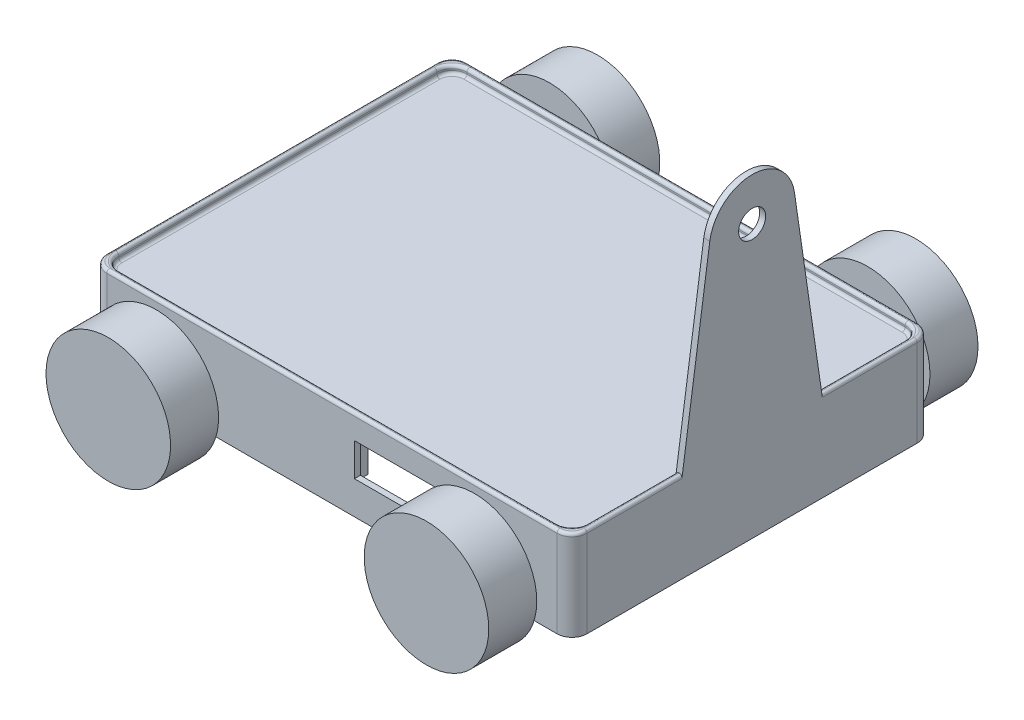
SolidWorks part; units mm, degrees
ref_plane "Front Plane" through (0, 0, 0) normal (0, 0, 1) x (1, 0, 0)
ref_plane "Top Plane" through (0, 0, 0) normal (0, 1, 0) x (1, 0, 0)
ref_plane "Right Plane" through (0, 0, 0) normal (1, 0, 0) x (0, 0, -1)
sketch "Sketch1" plane through (0, 0, 0) normal (0, 1, 0) x (1, 0, 0)
  line L1 (-160, 120) -> (160, 120)
  line L2 (-160, 120) -> (-160, -120)
  line L3 (-160, -120) -> (160, -120)
  line L4 (160, 120) -> (160, -120)
  line L5 (-160, 120) -> (160, -120) construction
  line L6 (-160, -120) -> (160, 120) construction
  point P0 (0, 0)
  dimension "D1" = 320
  dimension "D2" = 240
extrude "Boss-Extrude1" add sketch "Sketch1" along normal blind 5
sketch "Sketch3" plane through (0, 5, 0) normal (0, 1, 0) x (1, 0, 0)
  line L0 (156, 116) -> (-156, 116)
  line L1 (-156, 116) -> (-156, -116)
  line L2 (-156, -116) -> (156, -116)
  line L3 (156, -116) -> (156, 116)
  line L4 (160, -120) -> (160, 120)
  line L5 (160, 120) -> (-160, 120)
  line L6 (-160, 120) -> (-160, -120)
  line L7 (-160, -120) -> (160, -120)
  line L8 (160, -120) -> (160, 120)
  line L9 (160, 120) -> (-160, 120)
  line L10 (-160, 120) -> (-160, -120)
  line L11 (-160, -120) -> (160, -120)
  dimension "D1" = 0
  dimension "D2" = 4
extrude "Boss-Extrude3" add sketch "Sketch3" along normal blind 5
sketch "Sketch6" plane through (0, 0, 0) normal (0, -1, 0) x (1, 0, 0)
  line L0 (-156, 116) -> (-156, -116)
  line L1 (-156, -116) -> (156, -116)
  line L2 (156, -116) -> (156, 116)
  line L3 (156, 116) -> (-156, 116)
  line L4 (160, -120) -> (160, 120)
  line L5 (160, 120) -> (-160, 120)
  line L6 (-160, 120) -> (-160, -120)
  line L7 (-160, -120) -> (160, -120)
  line L8 (160, -120) -> (160, 120)
  line L9 (160, 120) -> (-160, 120)
  line L10 (-160, 120) -> (-160, -120)
  line L11 (-160, -120) -> (160, -120)
  dimension "D1" = 0
  dimension "D2" = 4
extrude "Boss-Extrude6" add sketch "Sketch6" along normal blind 50
fillet "Fillet2" radius 10 12 edges at (156, -25, -116) (156, -25, 116) (-156, -25, 116) (-156, -25, -116) (-160, -20, 120) (160, -20, 120) (160, -20, -120) (-160, -20, -120) (-156, 7.5, 116) (156, 7.5, 116) (156, 7.5, -116) (-156, 7.5, -116)
sketch "Sketch7" plane through (0, 0, 0) normal (0, -1, 0) x (1, 0, 0)
  line L0 (-156, 106) -> (-156, -106) construction
  line L1 (-126, -113) -> (-86, -113)
  line L2 (-126, -113) -> (-126, -73)
  line L3 (-126, -73) -> (-86, -73)
  line L4 (-86, -113) -> (-86, -73)
  line L5 (-126, -113) -> (-86, -73) construction
  line L6 (-126, -73) -> (-86, -113) construction
  line L7 (-146, -116) -> (146, -116) construction
  point P0 (-106, -93)
  point P5 (-93.4978, -78.3854)
  dimension "D1" = 40
  dimension "D2" = 40
  dimension "D3" = 50
  dimension "D4" = 23
extrude "Boss-Extrude7" add sketch "Sketch7" along normal blind 2 separate body
sketch "Sketch8" plane through (0, -2, 0) normal (0, -1, 0) x (1, 0, 0)
  line L0 (-86, -113) -> (-86, -73) construction
  line L1 (-126, -113) -> (-86, -113)
  line L2 (-126, -113) -> (-126, -111)
  line L3 (-126, -111) -> (-86, -111)
  line L4 (-86, -113) -> (-86, -111)
  dimension "D1" = 2
extrude "Boss-Extrude8" add sketch "Sketch8" along normal blind 45
fillet "Fillet3" radius 20 2 edges at (-126, -47, -112) (-86, -47, -112)
sketch "Sketch9" plane through (0, 0, -111) normal (0, 0, 1) x (1, 0, 0)
  circle A0 centre (-106, -27) radius 10
  dimension "D1" = 20
extrude "Cut-Extrude1" cut sketch "Sketch9" against normal through all
sketch "Sketch16" plane through (0, -2, 0) normal (0, -1, 0) x (1, 0, 0)
  line L0 (-91, -81) -> (-91, -105) construction
  line L1 (-91, -105) -> (-121, -105) construction
  line L2 (-121, -105) -> (-121, -81) construction
  line L3 (-121, -81) -> (-91, -81) construction
  line L4 (-106, -81) -> (-106, -73) construction
  line L5 (-86, -73) -> (-126, -73) construction
  circle A0 centre (-91, -81) radius 1.5
  circle A1 centre (-91, -105) radius 1.5
  circle A2 centre (-121, -81) radius 1.5
  circle A3 centre (-121, -105) radius 1.5
  dimension "D1" = 3
  dimension "D2" = 30
  dimension "D3" = 24
  dimension "D4" = 8
extrude "Cut-Extrude2" cut sketch "Sketch16" against normal up to surface (2 mm away) up to face at (0, 0, 0)
sketch "Sketch18" plane through (0, 0, 0) normal (0, -1, 0) x (1, 0, 0)
  circle A0 centre (-91, -81) radius 1.95
  circle A1 centre (-91, -105) radius 1.95
  circle A2 centre (-121, -105) radius 1.95
  circle A3 centre (-121, -81) radius 1.95
  dimension "D1" = 3.9
extrude "Cut-Extrude3" cut sketch "Sketch18" against normal blind 3.5
sketch "Sketch11" plane through (0, 0, -111) normal (0, 0, 1) x (1, 0, 0)
  circle A0 centre (-106, -27) radius 15
  dimension "D1" = 30
extrude "Boss-Extrude9" add sketch "Sketch11" along normal blind 45
sketch "Sketch12" plane through (0, 0, -111) normal (0, 0, -1) x (-1, 0, 0)
  circle A0 centre (106, -27) radius 2.6075
extrude "Boss-Extrude10" add sketch "Sketch12" along normal blind 20
sketch "Sketch15" plane through (0, 0, -131) normal (0, 0, -1) x (-1, 0, 0)
  circle A0 centre (106, -27) radius 41.5
  circle A1 centre (106, -27) radius 2.6075 construction
  point P2 (0, 0)
  dimension "D1" = 83
extrude "Boss-Extrude11" add sketch "Sketch15" along normal blind 32
sketch "Sketch22" plane through (0, -50, 0) normal (0, -1, 0) x (1, 0, 0)
  line L0 (152, -106) -> (152, 106)
  line L1 (146, 112) -> (-146, 112)
  line L2 (-152, 106) -> (-152, -106)
  line L3 (-146, -112) -> (146, -112)
  line L4 (-146, -116) -> (146, -116)
  line L5 (156, -106) -> (156, 106)
  line L6 (146, 116) -> (-146, 116)
  line L7 (-156, 106) -> (-156, -106)
  line L8 (-146, -116) -> (146, -116)
  line L9 (156, -106) -> (156, 106)
  line L10 (146, 116) -> (-146, 116)
  line L11 (-156, 106) -> (-156, -106)
  arc A0 (152, 106) -> (146, 112) centre (146, 106) ccw
  arc A1 (-146, 112) -> (-152, 106) centre (-146, 106) ccw
  arc A2 (-152, -106) -> (-146, -112) centre (-146, -106) ccw
  arc A3 (146, -112) -> (152, -106) centre (146, -106) ccw
  arc A4 (146, -116) -> (156, -106) centre (146, -106) ccw
  arc A5 (156, 106) -> (146, 116) centre (146, 106) ccw
  arc A6 (-146, 116) -> (-156, 106) centre (-146, 106) ccw
  arc A7 (-156, -106) -> (-146, -116) centre (-146, -106) ccw
  arc A8 (146, -116) -> (156, -106) centre (146, -106) ccw
  arc A9 (156, 106) -> (146, 116) centre (146, 106) ccw
  arc A10 (-146, 116) -> (-156, 106) centre (-146, 106) ccw
  arc A11 (-156, -106) -> (-146, -116) centre (-146, -106) ccw
  dimension "D1" = 0
  dimension "D2" = 4
extrude "Boss-Extrude12" add sketch "Sketch22" against normal blind 4.5
sketch "Sketch23" plane through (0, -50, 0) normal (0, -1, 0) x (1, 0, 0)
  line L0 (-146, -112) -> (146, -112) construction
  line L1 (-86, -112) -> (-126, -112)
  line L2 (-86, -112) -> (-86, -115)
  line L3 (-86, -115) -> (-126, -115)
  line L4 (-126, -112) -> (-126, -115)
  line L5 (-106, -111) -> (-106, -112) construction
  dimension "D1" = 3
  dimension "D2" = 40
extrude "Cut-Extrude6" cut sketch "Sketch23" against normal up to next (4.5 mm away)
mirror "Mirror4" about plane through (0, 0, 0) normal (1, 0, 0) of "Cut-Extrude6", "Cut-Extrude1", "Cut-Extrude3"
mirror "Mirror5" about plane through (0, 0, 0) normal (0, 0, 1) of "Mirror4", "Cut-Extrude1", "Cut-Extrude3", "Cut-Extrude6"
sketch "Sketch19" plane through (0, -50, 0) normal (0, -1, 0) x (1, 0, 0)
  line L1 (-156, 0) -> (-160, 0) construction
  line L2 (-160, 110) -> (-160, -110) construction
  circle A0 centre (-156, 0) radius 1.95
  dimension "D1" = 3.9
  dimension "D2" = 4
extrude "Cut-Extrude4" cut sketch "Sketch19" against normal blind 3.5
pattern_linear "LPattern1" count 2 spacing 80 along (0, 0, -1) count 2 spacing 80 along (0, 0, 1) of "Cut-Extrude4"
mirror "Mirror6" about plane through (0, 0, 0) normal (1, 0, 0) of "LPattern1", "Cut-Extrude4"
sketch "Sketch20" plane through (0, -50, 0) normal (0, -1, 0) x (1, 0, 0)
  line L0 (0, -116) -> (0, -120) construction
  line L2 (-150, -120) -> (150, -120) construction
  circle A0 centre (0, -116) radius 1.95
  dimension "D1" = 3.9
  dimension "D2" = 4
extrude "Cut-Extrude5" cut sketch "Sketch20" against normal blind 3.5
pattern_linear "LPattern2" count 2 spacing 60 along (1, 0, 0) count 2 spacing 60 along (-1, 0, 0) of "Cut-Extrude5"
mirror "Mirror7" about plane through (0, 0, 0) normal (0, 0, 1) of "LPattern2", "Cut-Extrude5"
sketch "Sketch24" plane through (0, 0, 0) normal (0, -1, 0) x (1, 0, 0)
  line L1 (5, 110) -> (-5, 110)
  line L2 (5, 110) -> (5, -110)
  line L3 (5, -110) -> (-5, -110)
  line L4 (-5, 110) -> (-5, -110)
  line L5 (5, 110) -> (-5, -110) construction
  line L6 (5, -110) -> (-5, 110) construction
  point P0 (0, 0)
  dimension "D1" = 10
  dimension "D2" = 220
extrude "Boss-Extrude13" add sketch "Sketch24" along normal blind 15
sketch "Sketch25" plane through (0, -15, 0) normal (0, -1, 0) x (1, 0, 0)
  line L0 (-5, 110) -> (-5, -110) construction
  line L1 (5, -110) -> (-5, -110)
  line L2 (5, -110) -> (5, -80)
  line L3 (5, -80) -> (-5, -80)
  line L4 (-5, -110) -> (-5, -80)
  line L5 (5, -110) -> (5, 110) construction
  line L6 (5, -16.9831) -> (-5, -16.9831)
  line L7 (5, -16.9831) -> (5, 13.0169)
  line L8 (5, 13.0169) -> (-5, 13.0169)
  line L9 (-5, -16.9831) -> (-5, 13.0169)
  line L10 (-5, 110) -> (-5, -110) construction
  line L11 (5, 110) -> (-5, 110)
  line L12 (5, 110) -> (5, 80)
  line L13 (5, 80) -> (-5, 80)
  line L14 (-5, 110) -> (-5, 80)
  dimension "D1" = 30
extrude "Cut-Extrude7" cut sketch "Sketch25" against normal up to surface (15 mm away) up to face at (0, 0, 0)
sketch "Sketch27" plane through (5, 0, 0) normal (1, 0, 0) x (0, 0, -1)
  line L0 (31.9831, -7.5) -> (31.9831, -10.5022) construction
  line L1 (65, -10.5022) -> (67.6, -9.0011)
  line L2 (67.6, -9.0011) -> (67.6, -5.9989)
  line L3 (67.6, -5.9989) -> (65, -4.4978)
  line L4 (65, -4.4978) -> (62.4, -5.9989)
  line L5 (62.4, -5.9989) -> (62.4, -9.0011)
  line L6 (62.4, -9.0011) -> (65, -10.5022)
  line L7 (34.5831, -9.0011) -> (34.5831, -5.9989)
  line L8 (34.5831, -5.9989) -> (31.9831, -4.4978)
  line L9 (31.9831, -4.4978) -> (29.3831, -5.9989)
  line L10 (29.3831, -5.9989) -> (29.3831, -9.0011)
  line L11 (29.3831, -9.0011) -> (31.9831, -10.5022)
  line L12 (31.9831, -10.5022) -> (34.5831, -9.0011)
  line L13 (80, -7.5) -> (65, -7.5) construction
  line L14 (80, 0) -> (80, -15) construction
  line L15 (65, -7.5) -> (31.9831, -7.5) construction
  line L16 (31.9831, -7.5) -> (16.9831, -7.5) construction
  line L17 (16.9831, 0) -> (16.9831, -15) construction
  circle A0 centre (65, -7.5) radius 2.6 construction
  circle A1 centre (31.9831, -7.5) radius 2.6 construction
  point P9 (67.6, -7.5)
  point P18 (65, -7.5)
  dimension "D1" = 5.2
  dimension "D2" = 5.2
  dimension "D3" = 15
extrude "Cut-Extrude8" cut sketch "Sketch27" against normal blind 2
sketch "Sketch28" plane through (-5, 0, 0) normal (-1, 0, 0) x (0, 0, 1)
  line L0 (-16.9831, -7.5) -> (-31.9831, -7.5) construction
  line L1 (-16.9831, 0) -> (-16.9831, -15) construction
  line L2 (-31.9831, -7.5) -> (-65, -7.5) construction
  line L3 (-65, -7.5) -> (-80, -7.5) construction
  line L4 (-80, 0) -> (-80, -15) construction
  circle A0 centre (-31.9831, -7.5) radius 2.95
  circle A1 centre (-65, -7.5) radius 2.95
  dimension "D2" = 5.9
  dimension "D1" = 15
extrude "Cut-Extrude9" cut sketch "Sketch28" against normal blind 2
sketch "Sketch29" plane through (-3, 0, 0) normal (-1, 0, 0) x (0, 0, 1)
  circle A0 centre (-31.9831, -7.5) radius 1.3
  circle A1 centre (-65, -7.5) radius 1.3
  dimension "D1" = 2.6
extrude "Cut-Extrude10" cut sketch "Sketch29" against normal up to next (6 mm away)
mirror "Mirror8" about plane through (0, 0, 0) normal (0, 0, 1) of "Cut-Extrude8", "Cut-Extrude9", "Cut-Extrude10"
sketch "Sketch30" plane through (0, 0, 116) normal (0, 0, -1) x (-1, 0, 0)
  line L0 (-146, 0) -> (146, 0) construction
  line L1 (5, 0) -> (-5, 0)
  line L2 (5, 0) -> (5, -40)
  line L3 (5, -40) -> (-5, -40)
  line L4 (-5, 0) -> (-5, -40)
  point P6 (0, 0)
  point P8 (0, 0)
  point P9 (0, 0)
  dimension "D1" = 10
  dimension "D2" = 40
extrude "Boss-Extrude14" add sketch "Sketch30" along normal blind 15
sketch "Sketch31" plane through (5, 0, 0) normal (1, 0, 0) x (0, 0, -1)
  line L0 (-108.5, -10) -> (-108.5, -13.0022) construction
  line L1 (-108.5, -33.0022) -> (-105.9, -31.5011)
  line L2 (-105.9, -31.5011) -> (-105.9, -28.4989)
  line L3 (-105.9, -28.4989) -> (-108.5, -26.9978)
  line L4 (-108.5, -26.9978) -> (-111.1, -28.4989)
  line L5 (-111.1, -28.4989) -> (-111.1, -31.5011)
  line L6 (-111.1, -31.5011) -> (-108.5, -33.0022)
  line L7 (-105.9, -11.5011) -> (-105.9, -8.4989)
  line L8 (-105.9, -8.4989) -> (-108.5, -6.9978)
  line L9 (-108.5, -6.9978) -> (-111.1, -8.4989)
  line L10 (-111.1, -8.4989) -> (-111.1, -11.5011)
  line L11 (-111.1, -11.5011) -> (-108.5, -13.0022)
  line L12 (-108.5, -13.0022) -> (-105.9, -11.5011)
  line L13 (-108.5, -40) -> (-108.5, -30) construction
  line L15 (-101, -40) -> (-116, -40) construction
  line L16 (-108.5, -30) -> (-108.5, -10) construction
  line L18 (-108.5, -10) -> (-108.5, 0) construction
  line L19 (-101, 0) -> (-116, 0) construction
  circle A0 centre (-108.5, -30) radius 2.6 construction
  circle A1 centre (-108.5, -10) radius 2.6 construction
  point P9 (-105.9, -30)
  dimension "D1" = 5.2
  dimension "D2" = 5.2
  dimension "D3" = 10
extrude "Cut-Extrude11" cut sketch "Sketch31" against normal blind 2
sketch "Sketch32" plane through (-5, 0, 0) normal (-1, 0, 0) x (0, 0, 1)
  line L0 (108.5, 0) -> (108.5, -10) construction
  line L2 (101, 0) -> (116, 0) construction
  line L3 (108.5, -10) -> (108.5, -30) construction
  line L5 (108.5, -30) -> (108.5, -40) construction
  line L6 (101, -40) -> (116, -40) construction
  circle A0 centre (108.5, -10) radius 2.95
  circle A1 centre (108.5, -30) radius 2.95
  dimension "D2" = 5.9
  dimension "D1" = 10
extrude "Cut-Extrude12" cut sketch "Sketch32" against normal blind 2
sketch "Sketch33" plane through (-3, 0, 0) normal (-1, 0, 0) x (0, 0, 1)
  circle A0 centre (108.5, -10) radius 1.3
  circle A1 centre (108.5, -30) radius 1.3
  dimension "D1" = 2.6
extrude "Cut-Extrude13" cut sketch "Sketch33" against normal up to next (6 mm away)
mirror "Mirror9" about plane through (0, 0, 0) normal (0, 0, 1) of "Cut-Extrude13", "Cut-Extrude12", "Cut-Extrude11", "Boss-Extrude14"
sketch "Sketch34" plane through (0, 0, 0) normal (0, -1, 0) x (1, 0, 0)
  line L0 (67.5, 36) -> (18.5, 36) construction
  line L1 (18.5, 36) -> (18.5, 94) construction
  line L2 (18.5, 94) -> (67.5, 94) construction
  line L3 (67.5, 94) -> (67.5, 36) construction
  line L4 (146, 116) -> (5, 116) construction
  line L5 (5, 101) -> (5, 116) construction
  circle A0 centre (67.5, 36) radius 1.95
  circle A1 centre (18.5, 36) radius 1.95
  circle A2 centre (67.5, 94) radius 1.95
  circle A3 centre (18.5, 94) radius 1.95
  point P10 (6.3465, 115.4436)
  dimension "D1" = 3.9
  dimension "D5" = 13.5
  dimension "D2" = 58
  dimension "D3" = 49
  dimension "D4" = 22
extrude "Cut-Extrude14" cut sketch "Sketch34" against normal blind 3.5
sketch "Sketch35" plane through (0, 0, 0) normal (0, -1, 0) x (1, 0, 0)
  line L1 (70.0437, 29.7617) -> (14.0437, 29.7617)
  line L2 (70.0437, 29.7617) -> (70.0437, 114.7617)
  line L3 (70.0437, 114.7617) -> (14.0437, 114.7617)
  line L4 (14.0437, 29.7617) -> (14.0437, 114.7617)
  dimension "D1" = 85
  dimension "D2" = 56
extrude "Boss-Extrude15" add sketch "Sketch35" along normal blind 3.5 separate body
sketch "Sketch38" plane through (0, 0, 116) normal (0, 0, -1) x (-1, 0, 0)
  line L0 (-5, 0) -> (-5, -40) construction
  line L1 (-15, -6) -> (-71, -6)
  line L2 (-15, -6) -> (-15, -28)
  line L3 (-15, -28) -> (-71, -28)
  line L4 (-71, -6) -> (-71, -28)
  line L5 (-146, 0) -> (-5, 0) construction
  dimension "D1" = 56
  dimension "D2" = 22
  dimension "D3" = 10
  dimension "D4" = 6
extrude "Cut-Extrude15" cut sketch "Sketch38" against normal through all
sketch "Sketch39" plane through (0, 0, 0) normal (0, -1, 0) x (1, 0, 0)
  line L0 (5, -80) -> (5, -16.9831) construction
  line L1 (20, -100.6205) -> (58, -100.6205) construction
  line L2 (20, -100.6205) -> (20, -62.6205) construction
  line L3 (20, -62.6205) -> (58, -62.6205) construction
  line L4 (58, -100.6205) -> (58, -62.6205) construction
  line L5 (20, -100.6205) -> (58, -62.6205) construction
  line L6 (20, -62.6205) -> (58, -100.6205) construction
  circle A0 centre (20, -62.6205) radius 1.95
  circle A1 centre (58, -62.6205) radius 1.95
  circle A2 centre (58, -100.6205) radius 1.95
  circle A3 centre (20, -100.6205) radius 1.95
  point P0 (39, -81.6205)
  dimension "D3" = 3.9
  dimension "D1" = 38
  dimension "D2" = 38
  dimension "D4" = 15
extrude "Cut-Extrude16" cut sketch "Sketch39" against normal blind 3.5
mirror "Mirror10" about plane through (0, 0, 0) normal (1, 0, 0) of "Cut-Extrude16"
sketch "Sketch40" plane through (0, 0, 0) normal (0, -1, 0) x (1, 0, 0)
  line L0 (156, -106) -> (156, 106) construction
  line L1 (156, 12.5) -> (153, 12.5)
  line L2 (156, 12.5) -> (156, -12.5)
  line L3 (156, -12.5) -> (153, -12.5)
  line L4 (153, 12.5) -> (153, -12.5)
  point P6 (156, 0)
  point P7 (156, 0)
  point P8 (0, 0)
  dimension "D1" = 3
  dimension "D2" = 25
extrude "Cut-Extrude17" cut sketch "Sketch40" against normal through all
sketch "Sketch41" plane through (0, 0, 0) normal (0, -1, 0) x (1, 0, 0)
  line L1 (15.8513, -7.2274) -> (82.6533, -7.2274) construction
  line L2 (15.8513, -7.2274) -> (15.8513, 0.6466) construction
  line L3 (15.8513, 0.6466) -> (82.6533, 0.6466) construction
  line L4 (82.6533, -7.2274) -> (82.6533, 0.6466) construction
  circle A0 centre (82.6533, 0.6466) radius 1.95
  circle A1 centre (82.6533, -7.2274) radius 1.95
  circle A2 centre (15.8513, -7.2274) radius 1.95
  circle A3 centre (15.8513, 0.6466) radius 1.95
  dimension "D3" = 3.9
  dimension "D1" = 66.802
  dimension "D2" = 7.874
sketch "Sketch42" plane through (0, 0, 0) normal (0, -1, 0) x (-1, 0, 0)
  line L1 (146.5206, 45.7699) -> (8.5206, 45.7699)
  line L2 (146.5206, 45.7699) -> (146.5206, -49.2301)
  line L3 (146.5206, -49.2301) -> (8.5206, -49.2301)
  line L4 (8.5206, 45.7699) -> (8.5206, -49.2301)
  dimension "D1" = 138
  dimension "D2" = 95
extrude "Boss-Extrude16" add sketch "Sketch42" along normal blind 25 separate body
extrude "Cut-Extrude18" cut sketch "Sketch41" against normal blind 3.5
sketch "Sketch43" plane through (0, 0, 0) normal (0, -1, 0) x (1, 0, 0)
  line L0 (152, -106) -> (152, 106) construction
  line L1 (100.5, 33.1129) -> (136, 33.1129) construction
  line L2 (100.5, 33.1129) -> (100.5, -28.3871) construction
  line L3 (100.5, -28.3871) -> (136, -28.3871) construction
  line L4 (136, 33.1129) -> (136, -28.3871) construction
  circle A0 centre (100.5, 33.1129) radius 1.95
  circle A1 centre (136, 33.1129) radius 1.95
  circle A2 centre (136, -28.3871) radius 1.95
  circle A3 centre (100.5, -28.3871) radius 1.95
  dimension "D3" = 3.9
  dimension "D1" = 61.5
  dimension "D2" = 35.5
  dimension "D4" = 16
extrude "Cut-Extrude19" cut sketch "Sketch43" against normal blind 3.5
sketch "Sketch44" plane through (0, 0, 0) normal (0, -1, 0) x (1, 0, 0)
  line L1 (-75.4017, 88.3155) -> (-8.5997, 88.3155) construction
  line L2 (-75.4017, 88.3155) -> (-75.4017, 96.1895) construction
  line L3 (-75.4017, 96.1895) -> (-8.5997, 96.1895) construction
  line L4 (-8.5997, 88.3155) -> (-8.5997, 96.1895) construction
  circle A0 centre (-8.5997, 96.1895) radius 1.95
  circle A1 centre (-8.5997, 88.3155) radius 1.95
  circle A2 centre (-75.4017, 88.3155) radius 1.95
  circle A3 centre (-75.4017, 96.1895) radius 1.95
  dimension "D3" = 3.9
  dimension "D1" = 66.802
  dimension "D2" = 7.874
extrude "Cut-Extrude20" cut sketch "Sketch44" against normal blind 3.5
sketch "Sketch45" plane through (0, 0, 0) normal (0, -1, 0) x (1, 0, 0)
  line L0 (152, -106) -> (152, 106) construction
  line L1 (100.5, 43.5144) -> (136, 43.5144) construction
  line L2 (100.5, 43.5144) -> (100.5, -17.9856) construction
  line L3 (100.5, -17.9856) -> (136, -17.9856) construction
  line L4 (136, 43.5144) -> (136, -17.9856) construction
  circle A0 centre (100.5, 43.5144) radius 1.95
  circle A1 centre (136, 43.5144) radius 1.95
  circle A2 centre (136, -17.9856) radius 1.95
  circle A3 centre (100.5, -17.9856) radius 1.95
  dimension "D3" = 3.9
  dimension "D1" = 61.5
  dimension "D2" = 35.5
  dimension "D4" = 16
extrude "Cut-Extrude21" cut sketch "Sketch45" against normal blind 3.5
sketch "Sketch46" plane through (0, 0, 0) normal (0, -1, 0) x (1, 0, 0)
  line L0 (152, -106) -> (152, 106) construction
  line L1 (100.5, 52.5321) -> (136, 52.5321) construction
  line L2 (100.5, 52.5321) -> (100.5, -8.9679) construction
  line L3 (100.5, -8.9679) -> (136, -8.9679) construction
  line L4 (136, 52.5321) -> (136, -8.9679) construction
  circle A0 centre (100.5, 52.5321) radius 1.95
  circle A1 centre (136, 52.5321) radius 1.95
  circle A2 centre (136, -8.9679) radius 1.95
  circle A3 centre (100.5, -8.9679) radius 1.95
  dimension "D3" = 3.9
  dimension "D1" = 61.5
  dimension "D2" = 35.5
  dimension "D4" = 16
extrude "Cut-Extrude22" cut sketch "Sketch46" against normal blind 3.5
sketch "Sketch47" plane through (0, 0, 0) normal (0, -1, 0) x (1, 0, 0)
  line L1 (-61.4404, 61.5887) -> (-23.4404, 61.5887) construction
  line L2 (-61.4404, 61.5887) -> (-61.4404, 99.5887) construction
  line L3 (-61.4404, 99.5887) -> (-23.4404, 99.5887) construction
  line L4 (-23.4404, 61.5887) -> (-23.4404, 99.5887) construction
  line L5 (-61.4404, 61.5887) -> (-23.4404, 99.5887) construction
  line L6 (-61.4404, 99.5887) -> (-23.4404, 61.5887) construction
  circle A0 centre (-61.4404, 99.5887) radius 1.95
  circle A1 centre (-23.4404, 99.5887) radius 1.95
  circle A2 centre (-23.4404, 61.5887) radius 1.95
  circle A3 centre (-61.4404, 61.5887) radius 1.95
  point P0 (-42.4404, 80.5887)
  dimension "D3" = 3.9
  dimension "D1" = 38
  dimension "D2" = 38
extrude "Cut-Extrude23" cut sketch "Sketch47" against normal blind 3.5
sketch "Sketch48" plane through (0, 0, 0) normal (0, -1, 0) x (1, 0, 0)
  line L0 (-132.2907, 57.5) -> (-87.2907, 57.5) construction
  line L1 (-87.2907, 57.5) -> (-87.2907, -57.5) construction
  line L2 (-87.2907, -57.5) -> (-132.2907, -57.5) construction
  line L3 (-132.2907, -57.5) -> (-132.2907, 57.5) construction
  line L4 (-132.2907, 0) -> (-152, 0) construction
  line L5 (-152, 106) -> (-152, -106) construction
  circle A0 centre (-132.2907, 57.5) radius 1.95
  circle A1 centre (-87.2907, 57.5) radius 1.95
  circle A2 centre (-132.2907, -57.5) radius 1.95
  circle A3 centre (-87.2907, -57.5) radius 1.95
  dimension "D1" = 3.9
  dimension "D2" = 115
  dimension "D3" = 45
extrude "Cut-Extrude24" cut sketch "Sketch48" against normal blind 3.5
mirror "Mirror11" about plane through (0, 0, 0) normal (1, 0, 0) of bodies 114
mirror "Mirror12" about plane through (0, 0, 0) normal (0, 0, 1) of bodies 155 114
sketch "Sketch49" plane through (160, 0, 0) normal (1, 0, 0) x (0, 0, -1)
  line L0 (-28.2023, 135.6083) -> (-46.5, 10)
  line L1 (-110, 10) -> (110, 10) construction
  line L2 (-46.5, 10) -> (46.5, 10)
  line L3 (46.5, 10) -> (28.2023, 135.6083)
  circle A0 centre (0, 131.5) radius 28.5
  point P8 (0, 10)
  point P9 (0, 0)
  line M4 (110, 10) -> (-110, 10)
  dimension "D2" = 57
  dimension "D1" = 121.5
  dimension "D3" = 93
extrude "Boss-Extrude17" add sketch "Sketch49" against normal blind 4 contours A0 L0 L3 M4 | A0
sketch "Sketch50" plane through (160, 0, 0) normal (1, 0, 0) x (0, 0, -1)
  circle A0 centre (0, 131.5) radius 9
  dimension "D1" = 18
extrude "Cut-Extrude25" cut sketch "Sketch50" against normal through all
fillet "Fillet4" radius 2 9 edges at (160, 10, -78.25) (157.0711, 10, -117.0711) (0, 10, -120) (-157.0711, 10, -117.0711) (160, 10, 78.25) (157.0711, 10, 117.0711) (0, 10, 120) (-157.0711, 10, 117.0711) (-160, 10, 0)
fillet "Fillet5" radius 2 18 edges at (156, 5, -59.25) (153.0711, 5, -113.0711) (0, 5, -116) (156, 5, 59.25) (153.0711, 5, 113.0711) (0, 5, 116) (-153.0711, 5, 113.0711) (-156, 5, 0) (156, 10, 76.25) (153.0711, 10, 113.0711) (0, 10, 116) (-153.0711, 10, 113.0711) (-156, 10, 0) (156, 10, -76.25) (153.0711, 10, -113.0711) (0, 10, -116) (-153.0711, 5, -113.0711) (-153.0711, 10, -113.0711)
